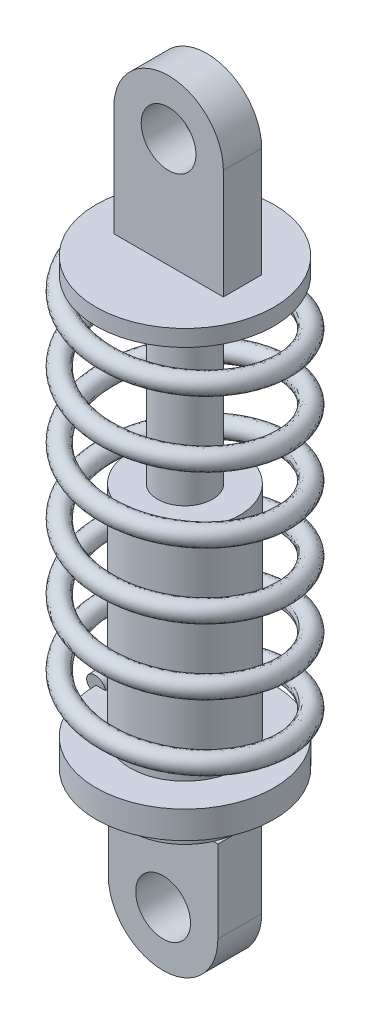
SolidWorks part; units mm, degrees
ref_plane "前视基准面" through (0, 0, 0) normal (0, 0, 1) x (1, 0, 0)
ref_plane "上视基准面" through (0, 0, 0) normal (0, 1, 0) x (1, 0, 0)
ref_plane "右视基准面" through (0, 0, 0) normal (1, 0, 0) x (0, 0, -1)
sketch "草图1" plane through (0, 0, 0) normal (0, 0, 1) x (1, 0, 0)
  line L1 (0, 0) -> (20, 0)
  line L2 (0, 0) -> (0, -25)
  line L3 (0, -25) -> (20, -25)
  line L4 (20, 0) -> (20, -25)
extrude "凸台-拉伸1" add sketch "草图1" along normal blind 8
sketch "草图2" plane through (0, 0, 8) normal (0, 0, 1) x (1, 0, 0)
  line L0 (10, 0) -> (10, -5) construction
  line L1 (20, 0) -> (0, 0) construction
  line L2 (20, -15) -> (22.4086, -15)
  line L3 (22.4086, -15) -> (25.4537, -29.8265)
  line L4 (25.4537, -29.8265) -> (9.4342, -31.683)
  line L5 (9.4342, -31.683) -> (-4.4104, -25.742)
  line L6 (-4.4104, -25.742) -> (0, -15)
  circle A0 centre (10, -15) radius 5
  arc A1 (0, -15) -> (20, -15) centre (10, -15) ccw
extrude "切除-拉伸1" cut sketch "草图2" against normal blind 8
sketch "草图3" plane through (0, 0, 0) normal (0, 1, 0) x (1, 0, 0)
  line L0 (0, -4) -> (20, -4) construction
  line L1 (0, -8) -> (0, 0) construction
  line L2 (20, -8) -> (20, 0) construction
  circle A0 centre (10, -4) radius 10
extrude "凸台-拉伸2" add sketch "草图3" along normal blind 5
sketch "草图4" plane through (0, 5, 0) normal (0, 1, 0) x (1, 0, 0)
  line L0 (10, 6) -> (10, -14) construction
  circle A0 centre (10, -4) radius 10 construction
  circle A1 centre (10, -4) radius 16.2408
extrude "凸台-拉伸3" add sketch "草图4" along normal blind 5
sketch "草图5" plane through (0, 10, 0) normal (0, 1, 0) x (1, 0, 0)
  line L0 (10, 12.2408) -> (10, -20.2408) construction
  circle A0 centre (10, -4) radius 16.2408 construction
  circle A1 centre (10, -4) radius 10
extrude "凸台-拉伸4" add sketch "草图5" along normal blind 40
sketch "草图6" plane through (0, 50, 0) normal (0, 1, 0) x (1, 0, 0)
  line L0 (10, 6) -> (10, -14) construction
  circle A0 centre (10, -4) radius 10 construction
  circle A1 centre (10, -4) radius 10 construction
  circle A2 centre (10, -4) radius 5
extrude "凸台-拉伸5" add sketch "草图6" along normal blind 33
sketch "草图7" plane through (0, 83, 0) normal (0, 1, 0) x (1, 0, 0)
  line L0 (10, 1) -> (10, -9) construction
  circle A0 centre (10, -4) radius 5 construction
  circle A1 centre (10, -4) radius 5 construction
  circle A2 centre (10, -4) radius 16.2408
extrude "凸台-拉伸6" add sketch "草图7" along normal blind 3
sketch "草图12" plane through (0, 10, 0) normal (0, 1, 0) x (1, 0, 0)
  line L0 (10, 12.2408) -> (10, -20.2408) construction
  circle A0 centre (10, -4) radius 16.2408 construction
  circle A1 centre (10, -4) radius 16.2408
curve "螺旋线/涡状线1" pitch 12 height 72 turns 6
sketch "草图14" plane through (0, 0, 0) normal (0, 0, 1) x (1, 0, 0)
  line L0 (26.2408, 10) -> (-6.2408, 10) construction
  circle A0 centre (-6.2408, 10) radius 1.7
  spline S0 degree 3 poles (-6.2408, 10) (-6.2408, 10.2232) (-5.5618, 10.6734) (-2.6314, 11.3457) (1.8508, 12.0187) (7.3342, 12.6916) (13.1451, 13.3645) (18.5696, 14.0374) (22.9413, 14.7103) (25.723, 15.3832) (26.5731, 16.0561) (25.3871, 16.729) (22.3107, 17.4019) (17.7218, 18.0748) (12.1843, 18.7477) (6.3784, 19.4206) (1.0174, 20.0935) (-3.24, 20.7664) (-5.8707, 21.4393) (-6.5517, 22.1121) (-5.1992, 22.785) (-1.9793, 23.4579) (2.7123, 24.1308) (8.2992, 24.8037) (14.095, 25.4766) (19.3878, 26.1495) (23.5272, 26.8224) (26.0048, 27.4953) (26.516, 28.1682) (24.9981, 28.8411) (21.6376, 29.514) (16.8474, 30.1869) (11.2159, 30.8598) (5.4351, 31.5327) (0.215, 32.2056) (-3.8029, 32.8785) (-6.125, 33.5514) (-6.466, 34.2243) (-4.7842, 34.8972) (-1.2859, 35.5701) (3.5988, 36.243) (9.27, 36.9159) (15.0309, 37.5888) (20.1737, 38.2617) (24.0666, 38.9346) (26.2313, 39.6075) (26.4019, 40.2804) (24.5574, 40.9533) (20.9245, 41.6262) (15.9494, 42.2991) (10.2434, 42.972) (4.5075, 43.6449) (-0.5536, 44.3178) (-4.3182, 44.9907) (-6.3237, 45.6636) (-6.3237, 46.3364) (-4.3182, 47.0093) (-0.5536, 47.6822) (4.5075, 48.3551) (10.2434, 49.028) (15.9494, 49.7009) (20.9245, 50.3738) (24.5574, 51.0467) (26.4019, 51.7196) (26.2313, 52.3925) (24.0666, 53.0654) (20.1737, 53.7383) (15.0309, 54.4112) (9.27, 55.0841) (3.5988, 55.757) (-1.2859, 56.4299) (-4.7842, 57.1028) (-6.466, 57.7757) (-6.125, 58.4486) (-3.8029, 59.1215) (0.215, 59.7944) (5.4351, 60.4673) (11.2159, 61.1402) (16.8474, 61.8131) (21.6376, 62.486) (24.9981, 63.1589) (26.516, 63.8318) (26.0048, 64.5047) (23.5272, 65.1776) (19.3878, 65.8505) (14.095, 66.5234) (8.2992, 67.1963) (2.7123, 67.8692) (-1.9793, 68.5421) (-5.1992, 69.215) (-6.5517, 69.8879) (-5.8707, 70.5607) (-3.24, 71.2336) (1.0174, 71.9065) (6.3784, 72.5794) (12.1843, 73.2523) (17.7218, 73.9252) (22.3107, 74.5981) (25.3871, 75.271) (26.5731, 75.9439) (25.723, 76.6168) (22.9413, 77.2897) (18.5696, 77.9626) (13.1451, 78.6355) (7.3342, 79.3084) (1.8508, 79.9813) (-2.6314, 80.6543) (-5.5618, 81.3266) (-6.2408, 81.7768) (-6.2408, 82) knots 0 0 0 0 0.009346 0.018692 0.028037 0.037383 0.046729 0.056075 0.065421 0.074766 0.084112 0.093458 0.102804 0.11215 0.121495 0.130841 0.140187 0.149533 0.158879 0.168224 0.17757 0.186916 0.196262 0.205607 0.214953 0.224299 0.233645 0.242991 0.252336 0.261682 0.271028 0.280374 0.28972 0.299065 0.308411 0.317757 0.327103 0.336449 0.345794 0.35514 0.364486 0.373832 0.383178 0.392523 0.401869 0.411215 0.420561 0.429907 0.439252 0.448598 0.457944 0.46729 0.476636 0.485981 0.495327 0.504673 0.514019 0.523364 0.53271 0.542056 0.551402 0.560748 0.570093 0.579439 0.588785 0.598131 0.607477 0.616822 0.626168 0.635514 0.64486 0.654206 0.663551 0.672897 0.682243 0.691589 0.700935 0.71028 0.719626 0.728972 0.738318 0.747664 0.757009 0.766355 0.775701 0.785047 0.794393 0.803738 0.813084 0.82243 0.831776 0.841121 0.850467 0.859813 0.869159 0.878505 0.88785 0.897196 0.906542 0.915888 0.925234 0.934579 0.943925 0.953271 0.962617 0.971963 0.981308 0.990654 1 1 1 1 construction
sweep "扫描1" add path "螺旋线/涡状线1" circular profile diameter 3.4 parameters "D3"=3.4
sketch "草图43" plane through (0, 0, 0) normal (0, 0, -1) x (-1, 0, 0)
  line L1 (6.2408, 86) -> (-26.2408, 86) construction
  line L4 (0, 86) -> (-20, 86)
  line L5 (-20, 86) -> (-20, 106)
  line L9 (0, 106) -> (0, 86)
  arc A4 (0, 106) -> (-20, 106) centre (-10, 106) ccw
  circle A5 centre (-10, 106) radius 5
  dimension "D1" = 20
  dimension "D2" = 10
extrude "凸台-拉伸7" add sketch "草图43" against normal blind 7
